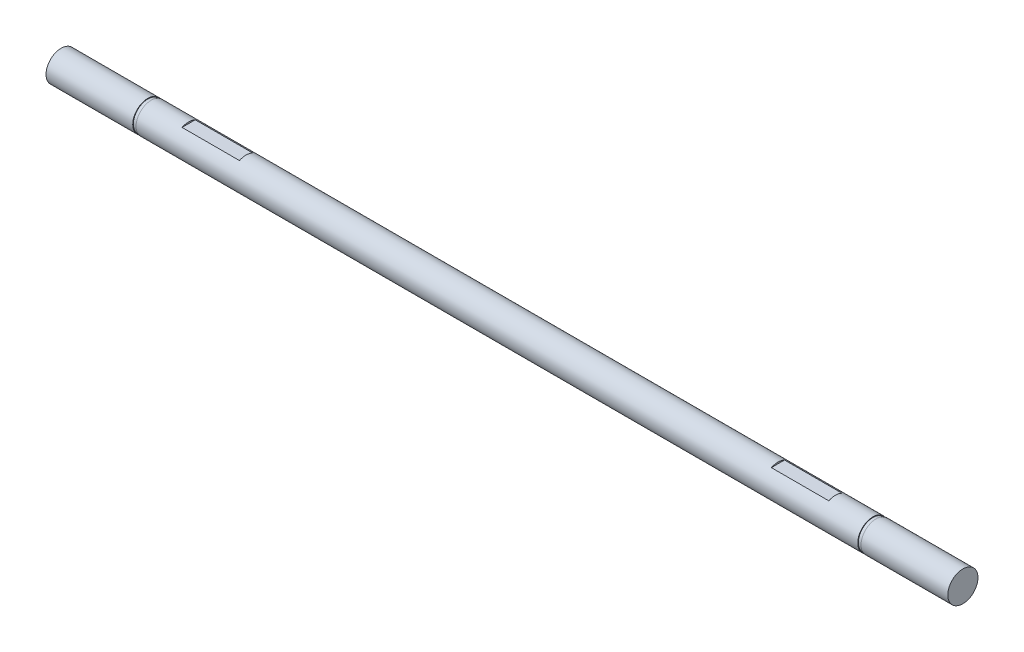
SolidWorks part; units mm, degrees
ref_plane "前视基准面" through (0, 0, 0) normal (0, 0, 1) x (1, 0, 0)
ref_plane "上视基准面" through (0, 0, 0) normal (0, 1, 0) x (1, 0, 0)
ref_plane "右视基准面" through (0, 0, 0) normal (1, 0, 0) x (0, 0, -1)
sketch "草图1" plane through (0, 0, 0) normal (1, 0, 0) x (0, 0, -1)
  line L0 (-2.1794, 4.5) -> (2.1794, 4.5)
  arc A0 (-2.1794, 4.5) -> (2.1794, 4.5) centre (0, 0) ccw
  dimension "D1" = 5
  dimension "D2" = 4.5
extrude "拉伸1" add sketch "草图1" along normal blind 19
sketch "草图2" plane through (19, 0, 0) normal (1, 0, 0) x (0, 0, -1)
  circle A0 centre (0, 0) radius 5
  dimension "D1" = 10
extrude "拉伸2" add sketch "草图2" along normal blind 16.2
sketch "草图5" plane through (0, 0, 0) normal (0, 1, 0) x (1, 0, 0)
  line L0 (35.2, 5) -> (0, 5) construction
  line L1 (31.4, 5) -> (32.5, 5)
  line L2 (31.4, 5) -> (31.4, 4.8)
  line L3 (31.4, 4.8) -> (32.5, 4.8)
  line L4 (32.5, 5) -> (32.5, 4.8)
  line L6 (35.2, -5) -> (35.2, 5) construction
  dimension "D1" = 1.1
  dimension "D2" = 3.8
  dimension "D3" = 0.2
revolve "切除-旋转1" cut sketch "草图5" angle 360 about axis through (19, 0, 0) along (-1, 0, 0)
sketch "草图4" plane through (0, 0, 0) normal (-1, 0, 0) x (0, 0, 1)
  circle A0 centre (0, 0) radius 5
extrude "拉伸4" add sketch "草图4" along normal blind 176
ref_plane "基准面1" through (-88, 0, 0) normal (-1, 0, 0) x (0, 0, 1)
mirror "镜向1" about plane through (-88, 0, 0) normal (-1, 0, 0) of "切除-旋转1", "拉伸1", "拉伸2"
sketch "草图6" plane through (35.2, 0, 0) normal (1, 0, 0) x (0, 0, -1)
  circle A0 centre (0, 0) radius 5
  circle A1 centre (0, 0) radius 5 construction
extrude "拉伸5" add sketch "草图6" along normal blind 26
sketch "草图7" plane through (-211.2, 0, 0) normal (-1, 0, 0) x (0, 0, 1)
  circle A0 centre (0, 0) radius 5
  circle A1 centre (0, 0) radius 5 construction
extrude "拉伸6" add sketch "草图7" along normal blind 26
